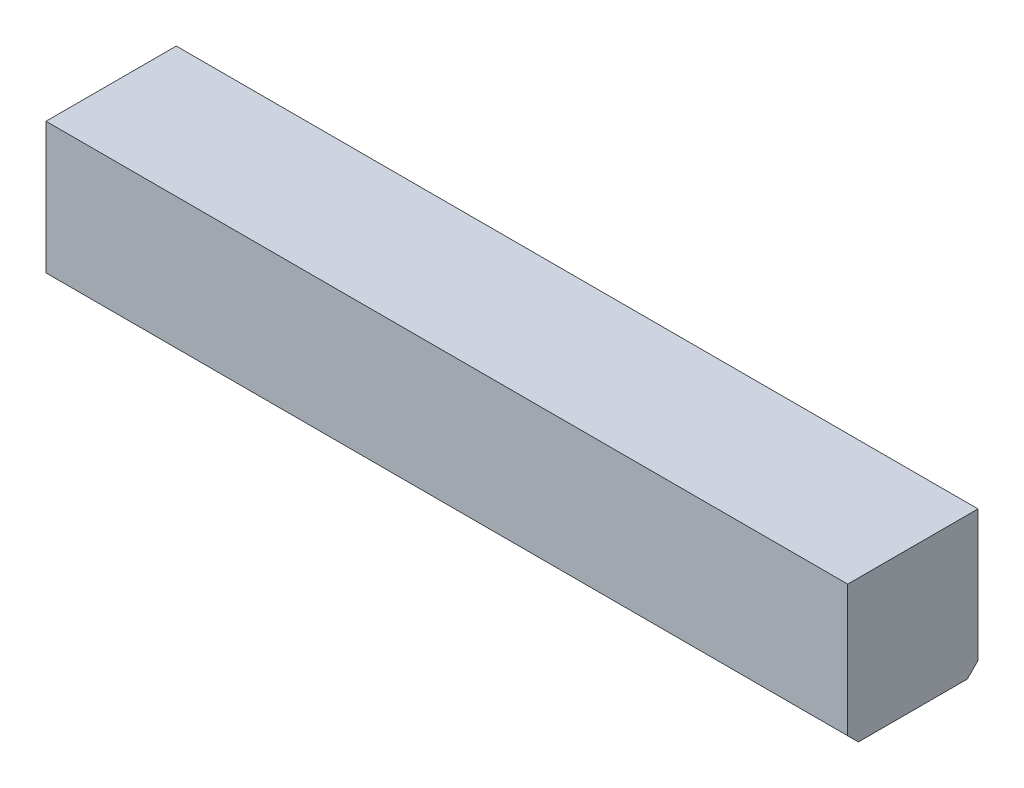
SolidWorks part; units mm, degrees
ref_plane "Front Plane" through (0, 0, 0) normal (0, 0, 1) x (1, 0, 0)
ref_plane "Top Plane" through (0, 0, 0) normal (0, 1, 0) x (1, 0, 0)
ref_plane "Right Plane" through (0, 0, 0) normal (1, 0, 0) x (0, 0, -1)
ref_plane "PX 30.000" through (30, 0, 0) normal (1, 0, 0) x (0, 0, -1)
sketch "spacer sketch" plane through (30, 0, 0) normal (1, 0, 0) x (0, 0, -1)
  line L0 (-0.8, 0) -> (0, 0.8)
  line L1 (0, 0.8) -> (0, 10.63)
  line L2 (0, 10.63) -> (-9.75, 10.63)
  line L3 (-9.75, 10.63) -> (-9.75, 0.8)
  line L4 (-9.75, 0.8) -> (-8.95, 0)
  line L5 (-8.95, 0) -> (-0.8, 0)
extrude "spacer" add sketch "spacer sketch" along normal mid plane 60
equation "\"diffL\"= 608.8mm"
equation "\"diffW\"= 329.4mm"
equation "\"diffT\"= 2.9mm"
equation "\"chanSlotW\"= 12.9mm"
equation "\"chanSlotDepth\"= 11.13mm"
equation "\"chanFloor\"= 1.57mm"
equation "\"chanLeg\"= 12.7mm"
equation "\"lightL\"= 604.8mm"
equation "\"lightW\"= 330.2mm"
equation "\"lightH\"= 92mm"
equation "\"lightSideFlat\"= 30mm"
equation "\"lightSlopeLen\"= 38.9mm"
equation "\"lightWingDepth\"= 50.1mm"
equation "\"lightWingFlat\"= 90.2mm"
equation "\"lightChanW\"= 99.6mm"
equation "\"lightChanStand\"= 44.1mm"
equation "\"insFlangeD\"= 12.3mm"
equation "\"insFromEnd\"= 20.7mm"
equation "\"insUpSlope\"= 20.8mm"
equation "\"gaugeH\"= 10mm"
equation "\"gaugeStepLen\"= 14mm"
equation "\"gaugeStepW0\"= 13.1mm"
equation "\"gaugeStepDW\"= 0.2mm"
equation "\"gaugeSteps\"= 5mm"
equation "\"gaugeHandleLen\"= 30mm"
equation "\"gaugeHandleW\"= 24mm"
equation "\"gaugeSlot0\"= 3mm"
equation "\"gaugeSlotD\"= 0.1mm"
equation "\"gaugeSlotDepth\"= 8mm"
equation "\"gap\"= 25.4mm"
equation "\"edgeL\"= 1mm"
equation "\"edgeW\"= 0.75mm"
equation "\"proud\"= 1.5mm"
equation "\"seatClr\"= 0.15mm"
equation "\"tongueClrZ\"= 0.1mm"
equation "\"tongueClrX\"= 0.25mm"
equation "\"tongueLen\"= 30mm"
equation "\"armSide\"= 45mm"
equation "\"armEnd\"= 20mm"
equation "\"cornerCham\"= 3mm"
equation "\"brkW\"= 26mm"
equation "\"brkT\"= 7mm"
equation "\"brkSeatClr\"= 0.3mm"
equation "\"brkScrewSpan\"= 16mm"
equation "\"pilotD\"= 2.7mm"
equation "\"pilotDepth\"= 10mm"
equation "\"screwClrD\"= 3.9mm"
equation "\"jogBelow\"= 4mm"
equation "\"padT\"= 7mm"
equation "\"padLen\"= 36mm"
equation "\"m6Clr\"= 7mm"
equation "\"m6Slot\"= 6mm"
equation "\"flangeRelD\"= 17mm"
equation "\"flangeRelDepth\"= 1.5mm"
equation "\"relLen\"= 5mm"
equation "\"relDepth\"= 3.3mm"
equation "\"knockN\"= 100mm"
equation "\"petgcfE\"= 3000mm"
equation "\"mockExtent\"= 110mm"
equation "\"relZnear\"= 9.4mm"
equation "\"relZfar\"= 23.4mm"
equation "\"headD\"= 8mm"
equation "\"headH\"= 2.5mm"
equation "\"headFromEnd\"= 6.8mm"
equation "\"headBack\"= 16.4mm"
equation "\"sideClr\"= 0.4mm"
equation "\"cornerRelR\"= 1.5mm"
equation "\"cornerRelBack\"= 0.6mm"
equation "\"endHeadH\"= 2.8mm"
equation "\"footClr\"= 1.2mm"
equation "\"footEndClr\"= 3.5mm"
equation "\"footLift\"= 6mm"
equation "\"footBlockClr\"= 0.5mm"
equation "\"footBack\"= 50mm"
equation "\"footFwd\"= 10mm"
equation "\"footRibH\"= 16mm"
equation "\"footRibT\"= 6mm"
equation "\"footBraceEnd\"= 3mm"
equation "\"footLoadN\"= 25mm"
equation "\"spacerLen\"= 60mm"
equation "\"spacerShort\"= 0.5mm"
equation "\"spacerCham\"= 0.8mm"
equation "\"spacerPerSide\"= 3mm"
equation "\"spacerPerEnd\"= 1mm"
equation "\"toolR\"= 9mm"
equation "\"visR\"= 4mm"
equation "\"edgeR\"= 1mm"
equation "\"bendOutR\"= 5mm"
equation "\"insideR\"= 2.5mm"
equation "\"footCornerR\"= 10mm"
equation "\"footFrontR\"= 8mm"
equation "\"braceKinkR\"= 12mm"
equation "\"bedCham\"= 1mm"
equation "\"bedChamSmall\"= 0.6mm"
equation "\"soleTopR\"= 2mm"
equation "\"cornerR\"= 6mm"
equation "\"rimInR\"= 1mm"
equation "\"insFlangeH\"= 1mm"
